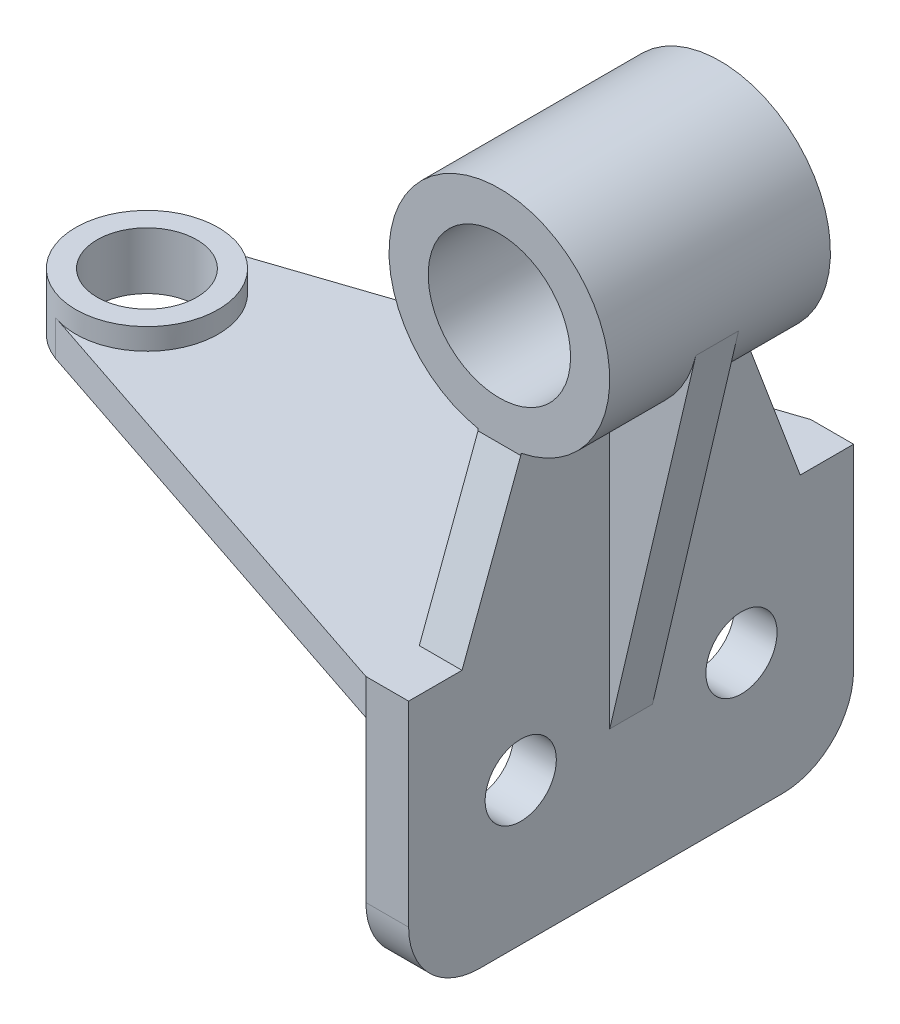
SolidWorks part; units mm, degrees
ref_plane "Front Plane" through (0, 0, 0) normal (0, 0, 1) x (1, 0, 0)
ref_plane "Top Plane" through (0, 0, 0) normal (0, 1, 0) x (1, 0, 0)
ref_plane "Right Plane" through (0, 0, 0) normal (1, 0, 0) x (0, 0, -1)
sketch "Sketch1" plane through (0, 0, 0) normal (0, 1, 0) x (1, 0, 0)
  line L0 (0, 0) -> (0, -62.5)
  line L1 (0, 0) -> (0, 62.5)
  line L2 (0, 62.5) -> (-12, 62.5)
  line L3 (-12, 62.5) -> (-142.3357, 18.97)
  line L4 (-136, 0) -> (27.2699, 0) construction
  line L5 (0, -62.5) -> (-12, -62.5)
  line L6 (-12, -62.5) -> (-142.9574, -18.7509)
  arc A0 (-142.3357, 18.97) -> (-142.9574, -18.7509) centre (-136, 0) ccw
  dimension "D1" = 20
  dimension "D2" = 125
  dimension "D3" = 136
  dimension "D4" = 12
extrude "Boss-Extrude1" add sketch "Sketch1" along normal blind 10
sketch "Sketch2" plane through (0, 10, 0) normal (0, 1, 0) x (1, 0, 0)
  circle A0 centre (-136, 0) radius 20
  arc A1 (-142.3357, 18.97) -> (-142.9574, -18.7509) centre (-136, 0) ccw construction
extrude "Boss-Extrude2" add sketch "Sketch2" along normal blind 6
sketch "Sketch3" plane through (0, 16, 0) normal (0, 1, 0) x (1, 0, 0)
  circle A0 centre (-136, 0) radius 14
extrude "Cut-Extrude1" cut sketch "Sketch3" against normal up to next
sketch "Sketch4" plane through (0, 0, 0) normal (0, 0, 1) x (1, 0, 0)
  line L0 (-6, 85) -> (-6, -22.4455) construction
  line L1 (0, 10) -> (0, 0) construction
  line L2 (-12, 10) -> (0, 10) construction
  circle A0 centre (-6, 85) radius 31
  circle A1 centre (-6, 85) radius 20
  dimension "D2" = 62
  dimension "D3" = 40
  dimension "D1" = 6
  dimension "D4" = 75
extrude "Boss-Extrude3" add sketch "Sketch4" along normal blind 31 and the other way blind 31 separate body
sketch "Sketch5" plane through (0, 0, 0) normal (1, 0, 0) x (0, 0, -1)
  line L0 (-47.5, 10) -> (-31, 54)
  line L1 (-62.5, 10) -> (62.5, 10) construction
  line L2 (-31, 54) -> (31, 54) construction
  line L3 (31, 54) -> (47.5, 10)
  line L4 (0, 10) -> (0, -7.8805) construction
  line L5 (-47.5, 10) -> (47.5, 10)
  line L6 (-31, 54) -> (-31, 60.6183)
  line L7 (-31, 116) -> (-31, 54) construction
  line L8 (-31, 60.6183) -> (31, 60.6183)
  line L9 (31, 54) -> (31, 116) construction
  line L10 (31, 60.6183) -> (31, 54)
  dimension "D1" = 95
extrude "Boss-Extrude4" add sketch "Sketch5" against normal blind 12
sketch "Sketch7" plane through (0, 0, 0) normal (1, 0, 0) x (0, 0, -1)
  line L0 (-62.5, 0) -> (-62.5, -45)
  line L1 (-42.5, -65) -> (42.5, -65)
  line L2 (62.5, -45) -> (62.5, 0)
  line L3 (-62.5, 10) -> (-47.5, 10) construction
  line L4 (0, 0) -> (0, -100.5164) construction
  line L5 (-62.5, 0) -> (62.5, 0) construction
  line L6 (-62.5, 0) -> (62.5, 0)
  arc A0 (62.5, -45) -> (42.5, -65) centre (42.5, -45) cw
  arc A1 (-62.5, -45) -> (-42.5, -65) centre (-42.5, -45) ccw
  circle A2 centre (-31, -25) radius 10
  circle A3 centre (31, -25) radius 10
  point P21 (-55, 10)
  dimension "D1" = 20
  dimension "D5" = 20
  dimension "D2" = 75
  dimension "D3" = 35
  dimension "D4" = 62
extrude "Boss-Extrude5" add sketch "Sketch7" against normal blind 12
sketch "Sketch8" plane through (0, 0, 0) normal (0, 0, 1) x (1, 0, 0)
  line L0 (24.1783, 77.9097) -> (0, -25)
  line L1 (0, 10) -> (0, -45) construction
  line L2 (0, -25) -> (0, 54.5862)
  line L4 (-141.7101, 10) -> (-12, 10) construction
  circle A0 centre (-6, 85) radius 31 construction
  circle A1 centre (-6, 85) radius 31
  point P7 (-170.4807, 51.6859)
  point P11 (-181.8001, 31.3111)
  dimension "D1" = 35
extrude "Boss-Extrude6" add sketch "Sketch8" along normal blind 6 and the other way blind 6 contours A1 L2 L0 region at (7.3416, 31.9887, 0)
sketch "Sketch9" plane through (0, 0, 0) normal (0, 0, 1) x (1, 0, 0)
  line L0 (-116, 10) -> (-28.9473, 105.8427)
  line L2 (-12, 54) -> (-12, 10) construction
  line L3 (-141.7101, 10) -> (-12, 10) construction
  line L4 (-12, 54) -> (-12, 10)
  line L5 (-116, 10) -> (-12, 10)
  arc A0 (0, 54.5862) -> (-12, 54.5862) centre (-6, 85) ccw construction
  arc A1 (-28.9473, 105.8427) -> (-12, 54.5862) centre (-6, 85) ccw
  point P1 (-26.0284, 108.6614)
  point P2 (0, 0)
  point P6 (-117.0837, 10)
